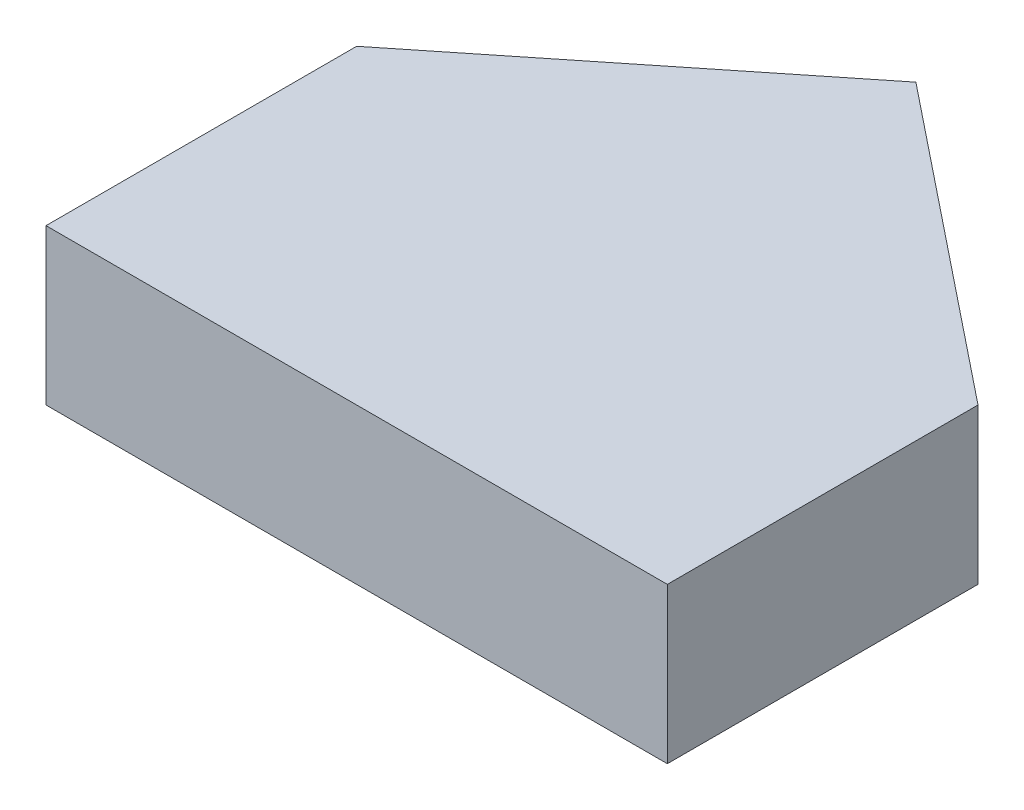
SolidWorks part; units mm, degrees
ref_plane "Front Plane" through (0, 0, 0) normal (0, 0, 1) x (1, 0, 0)
ref_plane "Top Plane" through (0, 0, 0) normal (0, 1, 0) x (1, 0, 0)
ref_plane "Right Plane" through (0, 0, 0) normal (1, 0, 0) x (0, 0, -1)
sketch "Sketch1" plane through (0, 0, 0) normal (0, 1, 0) x (1, 0, 0)
  line L0 (-10, 0) -> (0, 8)
  line L2 (-10, 0) -> (-10, -10)
  line L3 (-10, -10) -> (10, -10)
  line L4 (10, 0) -> (10, -10)
  line L5 (0, 8) -> (10, 0)
  line L6 (-10, 0) -> (10, 0) construction
  point P5 (0, 0)
  dimension "D1" = 10
  dimension "D2" = 20
  dimension "D3" = 8
extrude "Boss-Extrude1" add sketch "Sketch1" along normal blind 5
